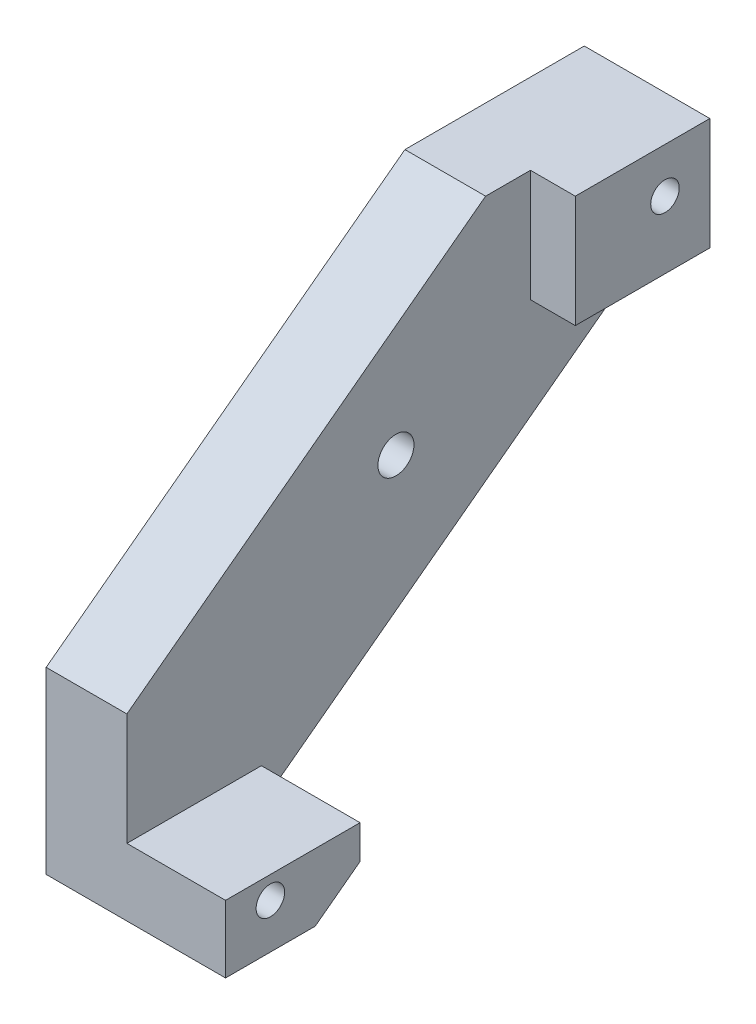
SolidWorks part; units mm, degrees
material "1060 Alloy"
ref_plane "Front Plane" through (0, 0, 0) normal (0, 0, 1) x (1, 0, 0)
ref_plane "Top Plane" through (0, 0, 0) normal (0, 1, 0) x (1, 0, 0)
ref_plane "Right Plane" through (0, 0, 0) normal (1, 0, 0) x (0, 0, -1)
sketch "Sketch1" plane through (0, 0, 0) normal (1, 0, 0) x (0, 0, -1)
  line L1 (-38.1, -31.75) -> (38.1, -31.75)
  line L2 (-38.1, -31.75) -> (-38.1, 31.75)
  line L3 (-38.1, 31.75) -> (38.1, 31.75)
  line L4 (38.1, -31.75) -> (38.1, 31.75)
  line L5 (-38.1, -31.75) -> (38.1, 31.75) construction
  line L6 (-38.1, 31.75) -> (38.1, -31.75) construction
  point P0 (0, 0)
  dimension "D1" = 76.2
  dimension "D2" = 63.5
extrude "Boss-Extrude1" add sketch "Sketch1" along normal blind 25.4
sketch "Sketch2" plane through (25.4, 0, 0) normal (1, 0, 0) x (0, 0, -1)
  line L0 (38.1, 31.75) -> (-38.1, 31.75) construction
  line L1 (-19.05, -31.75) -> (19.05, -31.75)
  line L2 (-19.05, -31.75) -> (-19.05, 31.75)
  line L3 (-19.05, 31.75) -> (19.05, 31.75)
  line L4 (19.05, -31.75) -> (19.05, 31.75)
  line L5 (-19.05, -31.75) -> (19.05, 31.75) construction
  line L6 (-19.05, 31.75) -> (19.05, -31.75) construction
  line L7 (-38.1, 31.75) -> (-38.1, -31.75) construction
  point P0 (0, 0)
  dimension "D1" = 19.05
extrude "Cut-Extrude1" cut sketch "Sketch2" against normal blind 13.97
hole_wizard "#10-32 Tapped Hole1" positions "Sketch6" profile "Sketch5" tap size "#10-32" standard "ANSI Inch"
sketch "Sketch6" plane through (25.4, 0, 0) normal (1, 0, 0) x (0, 0, -1)
  line L0 (-19.05, 31.75) -> (-38.1, 31.75) construction
  line L2 (-38.1, 31.75) -> (-38.1, -31.75) construction
  point P0 (-31.75, 25.4)
  dimension "D1" = 6.35
  dimension "D2" = 6.35
sketch "Sketch5" plane through (25.4, 25.4, 31.75) normal (0, 1, 0) x (0, 0, -1)
  line L0 (0, 0) -> (0, 14.9293)
  line L1 (0, 14.9293) -> (2.0193, 13.716)
  line L2 (2.0193, 13.716) -> (2.0193, 0)
  line L5 (2.0193, 0) -> (0, 0)
  line L10 (0, 14.9293) -> (-2.0193, 13.716) construction
  line L11 (0, -6.35) -> (0, 107.95) construction
  dimension "Tap Drill Dia." = 4.0386
  dimension "Tap Drill Depth" = 13.716
  dimension "Drill Angle" = 118
cosmetic thread "Hole Thread2" parameters "D1"=9.652, "D2"=4.826
hole_wizard "1/4-20 Tapped Hole1" positions "Sketch4" profile "Sketch3" tap size "1/4-20" standard "ANSI Inch"
sketch "Sketch4" plane through (11.43, 0, 0) normal (1, 0, 0) x (0, 0, -1)
  circle A0 centre (-31.75, 25.4) radius 2.0193 construction
  point P0 (0, 6.35)
  dimension "D1" = 0
  dimension "D2" = 19.05
sketch "Sketch3" plane through (11.43, 6.35, 0) normal (0, 1, 0) x (0, 0, -1)
  line L0 (0, 0) -> (0, 20.5838)
  line L1 (0, 20.5838) -> (2.5527, 19.05)
  line L2 (2.5527, 19.05) -> (2.5527, 0)
  line L5 (2.5527, 0) -> (0, 0)
  line L10 (0, 20.5838) -> (-2.5527, 19.05) construction
  line L11 (0, -6.35) -> (0, 107.95) construction
  dimension "Tap Drill Dia." = 5.1054
  dimension "Tap Drill Depth" = 19.05
  dimension "Drill Angle" = 118
cosmetic thread "Hole Thread1" parameters "D1"=5.08, "D2"=6.35
pattern_linear "LPattern1" count 2 spacing 50.8 along (0, -1, 0) count 2 spacing 63.5 along (0, 0, -1) of "#10-32 Tapped Hole1"
sketch "Sketch7" plane through (25.4, 0, 0) normal (1, 0, 0) x (0, 0, -1)
  line L0 (-38.1, 31.75) -> (-38.1, -31.75) construction
  line L1 (-38.1, 15.875) -> (38.1, 15.875)
  line L2 (-38.1, 15.875) -> (-38.1, -22.225)
  line L3 (-38.1, -22.225) -> (38.1, -22.225)
  line L4 (38.1, 15.875) -> (38.1, -22.225)
  line L6 (38.1, -31.75) -> (38.1, 31.75) construction
  circle A0 centre (-31.75, 25.4) radius 2.0193 construction
  dimension "D1" = 38.1
  dimension "D2" = 9.525
  dimension "D3" = 0
  dimension "D4" = 0
extrude "Cut-Extrude2" cut sketch "Sketch7" against normal up to surface (13.97 mm away) up to face at (11.43, 6.35, -2.5527)
sketch "Sketch8" plane through (0, 0, 0) normal (-1, 0, 0) x (0, 0, 1)
  line L0 (-38.1, 15.875) -> (25.4, -31.75)
  line L1 (38.1, -31.75) -> (-38.1, -31.75) construction
  line L2 (25.4, -31.75) -> (38.1, -31.75)
  line L3 (38.1, -31.75) -> (39.3192, -7.2644)
  line L5 (39.3192, -7.2644) -> (-12.7, 31.75)
  line L6 (-38.1, 31.75) -> (38.1, 31.75) construction
  line L7 (-12.7, 31.75) -> (-38.1, 31.75)
  line L8 (-38.1, 31.75) -> (-38.1, 15.875)
  dimension "D1" = 12.7
  dimension "D2" = 25.4
extrude "Cut-Extrude3" cut sketch "Sketch8" against normal through all flip side to cut
sketch "Sketch9" plane through (0, 0, -38.1) normal (0, 0, -1) x (-1, 0, 0)
  line L0 (-11.43, 15.875) -> (-25.4, 15.875) construction
  line L1 (-25.4, 31.75) -> (-17.78, 31.75)
  line L2 (-25.4, 31.75) -> (-25.4, 15.875)
  line L3 (-25.4, 15.875) -> (-17.78, 15.875)
  line L4 (-17.78, 31.75) -> (-17.78, 15.875)
  dimension "D1" = 7.62
extrude "Cut-Extrude4" cut sketch "Sketch9" against normal through all
